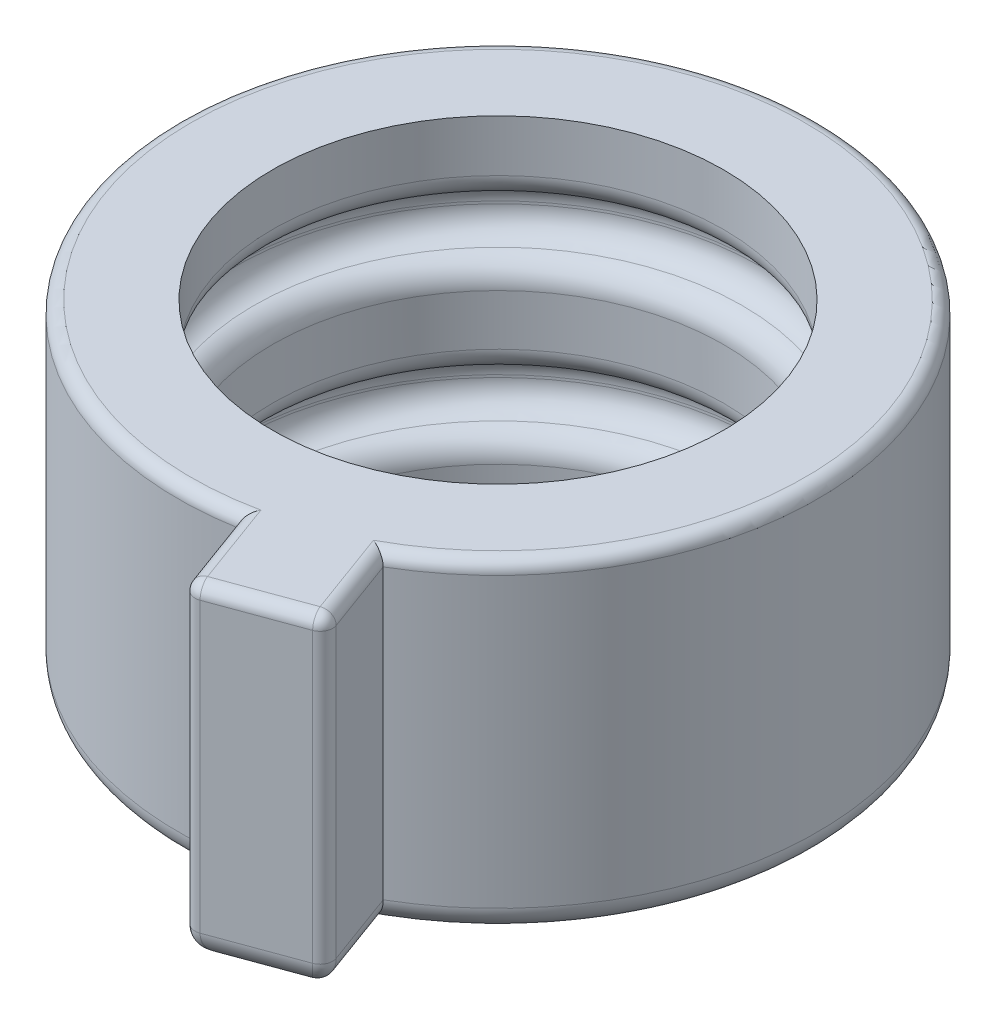
SolidWorks part; units mm, degrees
ref_plane "Спереди" through (0, 0, 0) normal (0, 0, 1) x (1, 0, 0)
ref_plane "Сверху" through (0, 0, 0) normal (0, 1, 0) x (1, 0, 0)
ref_plane "Справа" through (0, 0, 0) normal (1, 0, 0) x (0, 0, -1)
sketch "Эскиз1" plane through (0, 0, 0) normal (0, 1, 0) x (1, 0, 0)
  circle A0 centre (0, 0) radius 9
  circle A1 centre (0, 0) radius 12.75
  dimension "D1" = 18
  dimension "D2" = 25.5
extrude "Бобышка-Вытянуть1" add sketch "Эскиз1" along normal blind 13
sketch "Эскиз2" plane through (0, 13, 0) normal (0, 1, 0) x (1, 0, 0)
  circle A0 centre (0, 0) radius 10.5
  dimension "D1" = 21
extrude "Вырез-Вытянуть1" cut sketch "Эскиз2" against normal blind 2.1 from offset 3 offset against normal yes
extrude "Вырез-Вытянуть2" cut sketch "Эскиз2<2>" against normal blind 2.1 from offset 9 offset against normal yes
sketch "Эскиз2<2>" plane through (0, 13, 0) normal (0, 1, 0) x (1, 0, 0) same geometry as "Эскиз2"
fillet "Скругление1" radius 1 4 edges at (0, 4, 10.5) (0, 10, 10.5) (0, 7.9, 10.5) (0, 1.9, 10.5)
fillet "Скругление2" radius 1 4 edges at (0, 4, 9) (0, 1.9, 9) (0, 7.9, 9) (0, 10, 9)
sketch "Эскиз7" plane through (0, 0, 0) normal (1, 0, 0) x (0, 0, -1)
  line L0 (0, 0) -> (0, 16.2141) construction
ref_plane "Плоскость1" through (0, 0, 0) normal (-0.9135, 0, 0.4067) x (0, 1, 0)
sketch "Эскиз4" plane through (0, 0, 0) normal (-0.9135, 0, 0.4067) x (0.4067, 0, 0.9135)
  line L0 (0, 6.9635) -> (0, 4.9365) construction
  line L2 (9, 6.9635) -> (-9, 6.9635) construction
  line L3 (9, 4.9365) -> (-9, 4.9365) construction
  circle A0 centre (0, 5.95) radius 1.25
  point P10 (0, 5.95)
  dimension "D1" = 2.5
extrude "Вырез-Вытянуть3" cut sketch "Эскиз4" along normal through all
sketch "Эскиз6" plane through (0, 13, 0) normal (0, 1, 0) x (1, 0, 0)
  line L0 (0, 0) -> (5.5734, -15.2111) construction
  line L2 (0, 0) -> (22.3464, 0) construction
  line L3 (3.4608, -15.9852) -> (7.6861, -14.437)
  line L4 (3.4608, -15.9852) -> (1.9372, -11.8271)
  line L6 (7.6861, -14.437) -> (6.1625, -10.2789)
  line L7 (3.4608, -15.9852) -> (4.9923, -10.8954) construction
  line L8 (3.2287, -11.5416) -> (7.6861, -14.437) construction
  arc A0 (1.9372, -11.8271) -> (6.1625, -10.2789) centre (0, 0) ccw
  point P3 (4.5413, -12.3942)
  point P6 (5.5734, -15.2111)
  dimension "D1" = 69.877
  dimension "D2" = 16.2
  dimension "D3" = 4.5
  dimension "D4" = 3
extrude "Бобышка-Вытянуть2" add sketch "Эскиз6" against normal up to surface (13 mm away) up to face at (0, 0, 12.75)
fillet "Скругление3" radius 0.5 6 edges at (-4.3865, 13, -11.9717) (7.6861, 6.5, 14.437) (3.4608, 6.5, 15.9852) (7.0582, 13, 12.7234) (5.5734, 13, 15.2111) (2.8329, 13, 14.2715)
fillet "Скругление4" radius 1 6 edges at (-4.3865, 0, -11.9717) (2.7469, 0, 14.0368) (3.5479, 0, 15.7973) (5.5734, 0, 15.2111) (7.4982, 0, 14.3499) (6.9722, 0, 12.4886)
